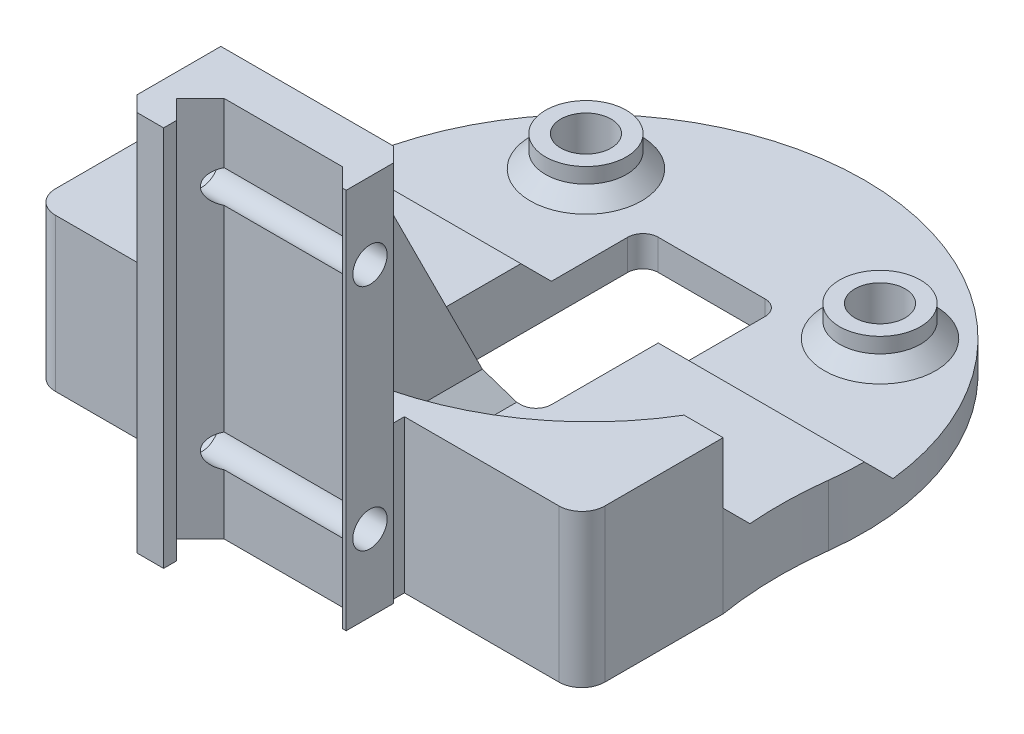
SolidWorks part; units mm, degrees
material "PETG"
ref_plane "Płaszczyzna przednia" through (0, 0, 0) normal (0, 0, 1) x (1, 0, 0)
ref_plane "Płaszczyzna górna" through (0, 0, 0) normal (0, 1, 0) x (1, 0, 0)
ref_plane "Płaszczyzna prawa" through (0, 0, 0) normal (1, 0, 0) x (0, 0, -1)
sketch "Sketch1" plane through (0, 0, 0) normal (0, 1, 0) x (1, 0, 0)
  circle A0 centre (0, 0) radius 36
  dimension "D1" = 72
extrude "Boss-Extrude1" add sketch "Sketch1" along normal blind 4
hole_wizard "Ø6.6 (6.6) Diameter Hole1" positions "Sketch2" profile "Sketch3" hole size "Ø6.6" standard "DIN" end condition up to next
sketch "Sketch2" plane through (0, 4, 0) normal (0, 1, 0) x (1, 0, 0)
  line L1 (19.0323, 19.0293) -> (-19.5051, 19.0293)
  point P0 (-19.5051, 19.0293)
  point P10 (19.0323, 19.0293)
  point P11 (19.0323, -19.508)
  point P12 (-19.5051, -19.508)
  dimension "D1" = 27.25
  dimension "D2" = 4
sketch "Sketch3" plane through (-19.5051, 4, -19.0293) normal (1, 0, 0) x (0, 0, 1)
  line L0 (0, 0) -> (0, 4)
  line L1 (0, 4) -> (3.3, 4)
  line L2 (3.3, 4) -> (3.3, 0)
  line L5 (3.3, 0) -> (0, 0)
  line L11 (0, -6.35) -> (0, 107.95) construction
  dimension "Thru Hole Dia." = 6.6
  dimension "Thru Hole Depth" = 4
sketch "Sketch4" plane through (0, 4, 0) normal (0, 1, 0) x (1, 0, 0)
  circle A0 centre (-19.5051, -19.508) radius 3.3 construction
  circle A1 centre (19.0323, -19.508) radius 3.3 construction
  circle A2 centre (19.0323, 19.0293) radius 3.3 construction
  circle A3 centre (-19.5051, 19.0293) radius 3.3 construction
  circle A4 centre (-19.5051, -19.508) radius 3.3
  circle A5 centre (19.0323, -19.508) radius 3.3
  circle A6 centre (19.0323, 19.0293) radius 3.3
  circle A7 centre (-19.5051, 19.0293) radius 3.3
  circle A8 centre (-19.5051, 19.0293) radius 5.3
  circle A9 centre (19.0323, 19.0293) radius 5.3
  circle A10 centre (19.0323, -19.508) radius 5.3
  circle A11 centre (-19.5051, -19.508) radius 5.3
  dimension "D1" = 2
extrude "Boss-Extrude2" add sketch "Sketch4" along normal blind 4
sketch "Sketch5" plane through (0, 0, 0) normal (0, -1, 0) x (1, 0, 0)
  line L0 (-36, 18.5) -> (-36, 37)
  line L2 (36, 37) -> (36, 18.5)
  line L3 (36, 18.5) -> (30.8828, 18.5)
  line L4 (-30.8828, 18.5) -> (-36, 18.5)
  line L5 (-36, 31.9282) -> (-17.5, 31.9282) construction
  line L10 (17.5, 31.7771) -> (36, 31.7771) construction
  line L11 (36, 37) -> (-36, 37)
  circle A0 centre (0, 0) radius 36 construction
  circle A4 centre (0, 0) radius 36
  arc A5 (30.8828, 18.5) -> (-30.8828, 18.5) centre (0, 0) ccw
  point P9 (0, 0)
  point P10 (37.4319, 37)
  dimension "D1" = 18.5
  dimension "D2" = 0
extrude "Boss-Extrude3" add sketch "Sketch5" against normal blind 20
fillet "Fillet1" radius 50 2 edges at (30.8828, 2, 18.5) (-30.8828, 2, 18.5)
fillet "Fillet2" radius 3 2 edges at (-36, 10, 37) (36, 10, 37)
sketch "Sketch7" plane through (0, 4, 0) normal (0, 1, 0) x (1, 0, 0)
  line L1 (-9, -16) -> (9, -16)
  line L2 (-9, -16) -> (-9, 16)
  line L3 (-9, 16) -> (9, 16)
  line L4 (9, -16) -> (9, 16)
  line L5 (-9, -16) -> (9, 16) construction
  line L6 (-9, 16) -> (9, -16) construction
  point P0 (0, 0)
  dimension "D1" = 32
  dimension "D2" = 18
extrude "Cut-Extrude2" cut sketch "Sketch7" against normal through all and the other way through all
fillet "Fillet5" radius 2 4 edges at (-9, 2, 16) (9, 2, 16) (9, 2, -16) (-9, 2, -16)
sketch "Sketch8" plane through (0, 4, 0) normal (0, 1, 0) x (1, 0, 0)
  line L0 (-36, 0) -> (-9, 0)
  line L1 (-9, 14) -> (-9, -14) construction
  line L2 (30.8828, -18.5) -> (36, -18.5)
  line L3 (-36, -18.5) -> (-30.8828, -18.5)
  line L4 (30.8828, -18.5) -> (36, -18.5)
  line L5 (-36, -18.5) -> (-30.8828, -18.5)
  line L6 (9, -14) -> (9, 14) construction
  line L7 (-7, -16) -> (7, -16) construction
  line L8 (9, -14) -> (9, 0)
  line L9 (-9, 0) -> (-9, -14)
  line L10 (-7, -16) -> (7, -16)
  line L11 (9, 0) -> (36, 0)
  arc A0 (-36, 0) -> (-35.7305, -4.3965) centre (0, 0) ccw
  arc A1 (-9, -14) -> (-7, -16) centre (-7, -14) ccw construction
  arc A2 (7, -16) -> (9, -14) centre (7, -14) ccw construction
  arc A3 (7, -16) -> (9, -14) centre (7, -14) ccw
  arc A4 (-9, -14) -> (-7, -16) centre (-7, -14) ccw
  circle A5 centre (19.0323, -19.508) radius 3.3 construction
  arc A6 (-30.8828, -18.5) -> (30.8828, -18.5) centre (0, 0) ccw
  arc A7 (35.7305, -4.3965) -> (36, -18.5) centre (85.3563, -10.5026) ccw
  arc A8 (35.7305, -4.3965) -> (-35.7305, -4.3965) centre (0, 0) ccw
  arc A9 (-36, -18.5) -> (-35.7305, -4.3965) centre (-85.3563, -10.5026) ccw
  arc A13 (35.7305, -4.3965) -> (36, -18.5) centre (85.3563, -10.5026) ccw
  arc A14 (35.7305, -4.3965) -> (36, 0) centre (0, 0) ccw
  arc A15 (-36, -18.5) -> (-35.7305, -4.3965) centre (-85.3563, -10.5026) ccw
  circle A18 centre (-19.5051, -19.508) radius 3.3 construction
  circle A19 centre (19.0323, -19.508) radius 3.3
  circle A20 centre (-19.5051, -19.508) radius 3.3
  arc A24 (-30.8828, -18.5) -> (30.8828, -18.5) centre (0, 0) ccw
  dimension "D1" = 0
extrude "Boss-Extrude4" add sketch "Sketch8" along normal up to surface (4 mm away) up to face at (-19.5051, 8, 24.808)
chamfer "Chamfer2" distance 4 angle 45 4 edges at (22.5, 4, 0) (-22.5, 4, 0) (33.4414, 8, 18.5) (-33.4414, 8, 18.5)
chamfer "Chamfer3" distance 2 angle 45 2 edges at (-19.5051, 4, -13.7293) (19.0323, 4, -13.7293)
sketch "Sketch9" plane through (0, 0, 0) normal (0, -1, 0) x (1, 0, 0)
  line L0 (-11.32, 50) -> (-5.82, 50)
  line L1 (-11.32, 37) -> (-11.32, 50)
  line L2 (-6.95, 44.45) -> (12.05, 44.45) construction
  line L3 (-5.82, 50) -> (-5.82, 48.32)
  line L4 (-5.82, 48.32) -> (-8.32, 45.82)
  line L5 (-8.32, 45.82) -> (-5.19, 42.69)
  line L6 (-5.19, 42.69) -> (10.29, 42.69)
  line L7 (10.29, 42.69) -> (13.22, 45.62)
  line L8 (13.22, 45.62) -> (13.22, 38.9)
  line L9 (13.22, 38.9) -> (11.32, 37)
  line L10 (-11.32, 37) -> (11.32, 37)
  line L11 (-6.95, 44.45) -> (-6.95, 47.19) construction
  line L12 (-6.95, 47.19) -> (12.05, 47.19) construction
  line L13 (12.05, 44.45) -> (12.05, 47.19) construction
  line L14 (0, 0) -> (0, 37) construction
  line L15 (33, 37) -> (-33, 37) construction
  line L16 (12.72, 45.12) -> (13.22, 45.12)
  line M27 (33, 37) -> (-33, 37)
  dimension "D1" = 5.5
  dimension "D2" = 1.68
  dimension "D3" = 13
  dimension "D4" = 45
  dimension "D5" = 19
  dimension "D6" = 2.74
  dimension "D7" = 4.5
  dimension "D8" = 45
  dimension "D9" = 3
  dimension "D10" = 1.9
  dimension "D11" = 24.54
  dimension "D12" = 0.5
extrude "Boss-Extrude5" add sketch "Sketch9" against normal blind 50 contours L16 L7 L6 L5 L4 L3 L0 L1 L9 L8 M27 region at (-0.8131, 0, 41.232)
ref_plane "Plane1" through (0.95, 0, 0) normal (1, 0, 0) x (0, 0, -1)
sketch "Sketch10" plane through (0.95, 0, 0) normal (1, 0, 0) x (0, 0, -1)
  line L0 (-37, 50) -> (-16, 8)
  line L1 (-16, 0) -> (-16, 8) construction
  line L2 (-16, 0) -> (-16, 8) construction
  line L3 (-37, 50) -> (-37, 20) construction
  line L4 (-37, 50) -> (-37, 20)
  line L5 (-37, 20) -> (-37, 8)
  line L6 (-37, 8) -> (-16, 8)
extrude "Boss-Extrude6" add sketch "Sketch10" along normal mid plane 5
chamfer "Chamfer4" distance 3 angle 45 8 edges at (-1.55, 8, 25.9833) (3.45, 14, 35.8343) (-1.55, 20, 36.4833) (-1.55, 35, 37) (-1.55, 14, 35.9666) (3.45, 8, 25.9172) (3.45, 20, 36.4172) (3.45, 35, 37) first distance on face at (-1.55, 21.2, 32.3866) first distance on face at (21.3277, 13.6065, 26.0943) first distance on face at (19.4688, 8, 13.2942) first distance on face at (22.3983, 20, 31.6746) first distance on face at (7.385, 35, 37)
sketch "Sketch11" plane through (13.22, 0, 0) normal (1, 0, 0) x (0, 0, -1)
  line L0 (-45.82, 50) -> (-45.82, 0) construction
  line L1 (-42, 30) -> (-42, 20) construction
  line L2 (-42, 25) -> (-50, 25) construction
  line L3 (-50, 50) -> (-50, 0) construction
  circle A0 centre (-42, 40) radius 2.25
  circle A1 centre (-42, 30) radius 2.25 construction
  circle A2 centre (-42, 20) radius 2.25 construction
  circle A3 centre (-42, 10) radius 2.25
  dimension "D1" = 3.82
  dimension "D2" = 4.5
  dimension "D4" = 10
  dimension "D5" = 30
  dimension "D3" = 4
extrude "Cut-Extrude3" cut sketch "Sketch11" against normal through all and the other way through all
chamfer "Chamfer5" distance 2 angle 45 2 edges at (-11.32, 25, 50) (11.32, 10, 37) first distance on face at (-11.32, 40, 39.75) first distance on face at (12.08, 24, 37.76)
sketch "Sketch12" plane through (-11.32, 0, 0) normal (-1, 0, 0) x (0, 0, 1)
  line L0 (42, 16.0163) -> (45.45, 18.0081) construction
  line L1 (42, 6.0163) -> (45.45, 8.0081)
  line L2 (45.45, 8.0081) -> (45.45, 11.9919)
  line L3 (45.45, 11.9919) -> (42, 13.9837)
  line L4 (42, 13.9837) -> (38.55, 11.9919)
  line L5 (38.55, 11.9919) -> (38.55, 8.0081)
  line L6 (38.55, 8.0081) -> (42, 6.0163)
  line L7 (45.45, 18.0081) -> (45.45, 21.9919) construction
  line L8 (45.45, 21.9919) -> (42, 23.9837) construction
  line L9 (42, 23.9837) -> (38.55, 21.9919) construction
  line L10 (38.55, 21.9919) -> (38.55, 18.0081) construction
  line L11 (38.55, 18.0081) -> (42, 16.0163) construction
  line L12 (42, 26.0163) -> (45.45, 28.0081) construction
  line L13 (45.45, 28.0081) -> (45.45, 31.9919) construction
  line L14 (45.45, 31.9919) -> (42, 33.9837) construction
  line L15 (42, 33.9837) -> (38.55, 31.9919) construction
  line L16 (38.55, 31.9919) -> (38.55, 28.0081) construction
  line L17 (38.55, 28.0081) -> (42, 26.0163) construction
  line L18 (42, 36.0163) -> (45.45, 38.0081)
  line L19 (45.45, 38.0081) -> (45.45, 41.9919)
  line L20 (45.45, 41.9919) -> (42, 43.9837)
  line L21 (42, 43.9837) -> (38.55, 41.9919)
  line L22 (38.55, 41.9919) -> (38.55, 38.0081)
  line L23 (38.55, 38.0081) -> (42, 36.0163)
  circle A0 centre (42, 10) radius 3.45 construction
  point P1 (38.55, 10)
  dimension "D1" = 6.9
  dimension "D2" = 4
extrude "Cut-Extrude4" cut sketch "Sketch12" against normal blind 2.5
